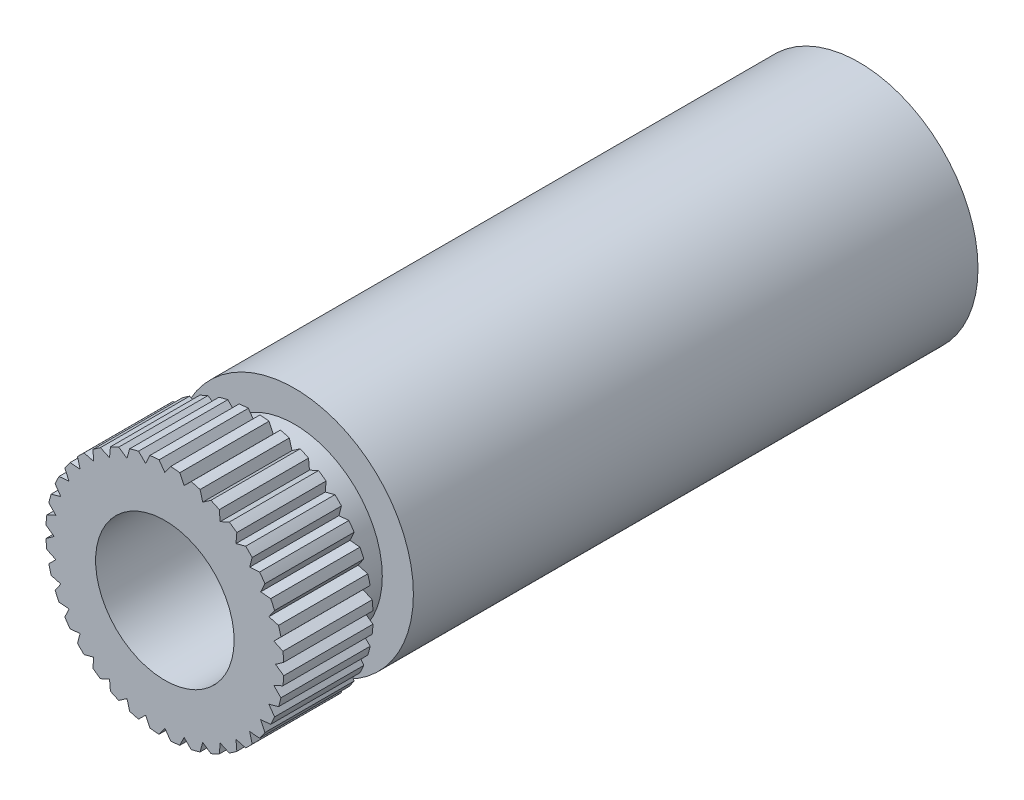
SolidWorks part; units mm, degrees
ref_plane "Front Plane" through (0, 0, 0) normal (0, 0, 1) x (1, 0, 0)
ref_plane "Top Plane" through (0, 0, 0) normal (0, 1, 0) x (1, 0, 0)
ref_plane "Right Plane" through (0, 0, 0) normal (1, 0, 0) x (0, 0, -1)
sketch "Sketch1" plane through (0, 0, 0) normal (0, 0, 1) x (1, 0, 0)
  circle A0 centre (0, 0) radius 6
extrude "Boss-Extrude1" add sketch "Sketch1" against normal blind 35
sketch "Sketch4" plane through (0, 0, 0) normal (0, 0, 1) x (1, 0, 0)
  line L0 (0, 0) -> (5.5808, 0)
  line L1 (6.2992, 0) -> (6.2992, 0.508)
  line L2 (6.2992, 0.508) -> (5.5808, 0)
  line L3 (5.5808, 0) -> (6.2992, -0.508)
  line L4 (6.2992, -0.508) -> (6.2992, 0)
  line L5 (6.2917, -0.5936) -> (5.4961, -0.9691)
  line L6 (5.4961, -0.9691) -> (6.1153, -1.5941)
  line L7 (6.1153, -1.5941) -> (6.2035, -1.0938)
  line L8 (6.2035, -1.0938) -> (6.2917, -0.5936)
  line L9 (6.0931, -1.6771) -> (5.2443, -1.9088)
  line L10 (5.2443, -1.9088) -> (5.7456, -2.6318)
  line L11 (5.7456, -2.6318) -> (5.9193, -2.1545)
  line L12 (5.9193, -2.1545) -> (6.0931, -1.6771)
  line L13 (5.7093, -2.7097) -> (4.8331, -2.7904)
  line L14 (4.8331, -2.7904) -> (5.2013, -3.5895)
  line L15 (5.2013, -3.5895) -> (5.4553, -3.1496)
  line L16 (5.4553, -3.1496) -> (5.7093, -2.7097)
  line L17 (5.152, -3.6599) -> (4.2752, -3.5873)
  line L18 (4.2752, -3.5873) -> (4.4989, -4.4382)
  line L19 (4.4989, -4.4382) -> (4.8255, -4.049)
  line L20 (4.8255, -4.049) -> (5.152, -3.6599)
  line L21 (4.4382, -4.4989) -> (3.5873, -4.2752)
  line L22 (3.5873, -4.2752) -> (3.6599, -5.152)
  line L23 (3.6599, -5.152) -> (4.049, -4.8255)
  line L24 (4.049, -4.8255) -> (4.4382, -4.4989)
  line L25 (3.5895, -5.2013) -> (2.7904, -4.8331)
  line L26 (2.7904, -4.8331) -> (2.7097, -5.7093)
  line L27 (2.7097, -5.7093) -> (3.1496, -5.4553)
  line L28 (3.1496, -5.4553) -> (3.5895, -5.2013)
  line L29 (2.6318, -5.7456) -> (1.9088, -5.2443)
  line L30 (1.9088, -5.2443) -> (1.6771, -6.0931)
  line L31 (1.6771, -6.0931) -> (2.1545, -5.9193)
  line L32 (2.1545, -5.9193) -> (2.6318, -5.7456)
  line L33 (1.5941, -6.1153) -> (0.9691, -5.4961)
  line L34 (0.9691, -5.4961) -> (0.5936, -6.2917)
  line L35 (0.5936, -6.2917) -> (1.0938, -6.2035)
  line L36 (1.0938, -6.2035) -> (1.5941, -6.1153)
  line L37 (0.508, -6.2992) -> (0, -5.5808)
  line L38 (0, -5.5808) -> (-0.508, -6.2992)
  line L39 (-0.508, -6.2992) -> (0, -6.2992)
  line L40 (0, -6.2992) -> (0.508, -6.2992)
  line L41 (-0.5936, -6.2917) -> (-0.9691, -5.4961)
  line L42 (-0.9691, -5.4961) -> (-1.5941, -6.1153)
  line L43 (-1.5941, -6.1153) -> (-1.0938, -6.2035)
  line L44 (-1.0938, -6.2035) -> (-0.5936, -6.2917)
  line L45 (-1.6771, -6.0931) -> (-1.9088, -5.2443)
  line L46 (-1.9088, -5.2443) -> (-2.6318, -5.7456)
  line L47 (-2.6318, -5.7456) -> (-2.1545, -5.9193)
  line L48 (-2.1545, -5.9193) -> (-1.6771, -6.0931)
  line L49 (-2.7097, -5.7093) -> (-2.7904, -4.8331)
  line L50 (-2.7904, -4.8331) -> (-3.5895, -5.2013)
  line L51 (-3.5895, -5.2013) -> (-3.1496, -5.4553)
  line L52 (-3.1496, -5.4553) -> (-2.7097, -5.7093)
  line L53 (-3.6599, -5.152) -> (-3.5873, -4.2752)
  line L54 (-3.5873, -4.2752) -> (-4.4382, -4.4989)
  line L55 (-4.4382, -4.4989) -> (-4.049, -4.8255)
  line L56 (-4.049, -4.8255) -> (-3.6599, -5.152)
  line L57 (-4.4989, -4.4382) -> (-4.2752, -3.5873)
  line L58 (-4.2752, -3.5873) -> (-5.152, -3.6599)
  line L59 (-5.152, -3.6599) -> (-4.8255, -4.049)
  line L60 (-4.8255, -4.049) -> (-4.4989, -4.4382)
  line L61 (-5.2013, -3.5895) -> (-4.8331, -2.7904)
  line L62 (-4.8331, -2.7904) -> (-5.7093, -2.7097)
  line L63 (-5.7093, -2.7097) -> (-5.4553, -3.1496)
  line L64 (-5.4553, -3.1496) -> (-5.2013, -3.5895)
  line L65 (-5.7456, -2.6318) -> (-5.2443, -1.9088)
  line L66 (-5.2443, -1.9088) -> (-6.0931, -1.6771)
  line L67 (-6.0931, -1.6771) -> (-5.9193, -2.1545)
  line L68 (-5.9193, -2.1545) -> (-5.7456, -2.6318)
  line L69 (-6.1153, -1.5941) -> (-5.4961, -0.9691)
  line L70 (-5.4961, -0.9691) -> (-6.2917, -0.5936)
  line L71 (-6.2917, -0.5936) -> (-6.2035, -1.0938)
  line L72 (-6.2035, -1.0938) -> (-6.1153, -1.5941)
  line L73 (-6.2992, -0.508) -> (-5.5808, 0)
  line L74 (-5.5808, 0) -> (-6.2992, 0.508)
  line L75 (-6.2992, 0.508) -> (-6.2992, 0)
  line L76 (-6.2992, 0) -> (-6.2992, -0.508)
  line L77 (-6.2917, 0.5936) -> (-5.4961, 0.9691)
  line L78 (-5.4961, 0.9691) -> (-6.1153, 1.5941)
  line L79 (-6.1153, 1.5941) -> (-6.2035, 1.0938)
  line L80 (-6.2035, 1.0938) -> (-6.2917, 0.5936)
  line L81 (-6.0931, 1.6771) -> (-5.2443, 1.9088)
  line L82 (-5.2443, 1.9088) -> (-5.7456, 2.6318)
  line L83 (-5.7456, 2.6318) -> (-5.9193, 2.1545)
  line L84 (-5.9193, 2.1545) -> (-6.0931, 1.6771)
  line L85 (-5.7093, 2.7097) -> (-4.8331, 2.7904)
  line L86 (-4.8331, 2.7904) -> (-5.2013, 3.5895)
  line L87 (-5.2013, 3.5895) -> (-5.4553, 3.1496)
  line L88 (-5.4553, 3.1496) -> (-5.7093, 2.7097)
  line L89 (-5.152, 3.6599) -> (-4.2752, 3.5873)
  line L90 (-4.2752, 3.5873) -> (-4.4989, 4.4382)
  line L91 (-4.4989, 4.4382) -> (-4.8255, 4.049)
  line L92 (-4.8255, 4.049) -> (-5.152, 3.6599)
  line L93 (-4.4382, 4.4989) -> (-3.5873, 4.2752)
  line L94 (-3.5873, 4.2752) -> (-3.6599, 5.152)
  line L95 (-3.6599, 5.152) -> (-4.049, 4.8255)
  line L96 (-4.049, 4.8255) -> (-4.4382, 4.4989)
  line L97 (-3.5895, 5.2013) -> (-2.7904, 4.8331)
  line L98 (-2.7904, 4.8331) -> (-2.7097, 5.7093)
  line L99 (-2.7097, 5.7093) -> (-3.1496, 5.4553)
  line L100 (-3.1496, 5.4553) -> (-3.5895, 5.2013)
  line L101 (-2.6318, 5.7456) -> (-1.9088, 5.2443)
  line L102 (-1.9088, 5.2443) -> (-1.6771, 6.0931)
  line L103 (-1.6771, 6.0931) -> (-2.1545, 5.9193)
  line L104 (-2.1545, 5.9193) -> (-2.6318, 5.7456)
  line L105 (-1.5941, 6.1153) -> (-0.9691, 5.4961)
  line L106 (-0.9691, 5.4961) -> (-0.5936, 6.2917)
  line L107 (-0.5936, 6.2917) -> (-1.0938, 6.2035)
  line L108 (-1.0938, 6.2035) -> (-1.5941, 6.1153)
  line L109 (-0.508, 6.2992) -> (0, 5.5808)
  line L110 (0, 5.5808) -> (0.508, 6.2992)
  line L111 (0.508, 6.2992) -> (0, 6.2992)
  line L112 (0, 6.2992) -> (-0.508, 6.2992)
  line L113 (0.5936, 6.2917) -> (0.9691, 5.4961)
  line L114 (0.9691, 5.4961) -> (1.5941, 6.1153)
  line L115 (1.5941, 6.1153) -> (1.0938, 6.2035)
  line L116 (1.0938, 6.2035) -> (0.5936, 6.2917)
  line L117 (1.6771, 6.0931) -> (1.9088, 5.2443)
  line L118 (1.9088, 5.2443) -> (2.6318, 5.7456)
  line L119 (2.6318, 5.7456) -> (2.1545, 5.9193)
  line L120 (2.1545, 5.9193) -> (1.6771, 6.0931)
  line L121 (2.7097, 5.7093) -> (2.7904, 4.8331)
  line L122 (2.7904, 4.8331) -> (3.5895, 5.2013)
  line L123 (3.5895, 5.2013) -> (3.1496, 5.4553)
  line L124 (3.1496, 5.4553) -> (2.7097, 5.7093)
  line L125 (3.6599, 5.152) -> (3.5873, 4.2752)
  line L126 (3.5873, 4.2752) -> (4.4382, 4.4989)
  line L127 (4.4382, 4.4989) -> (4.049, 4.8255)
  line L128 (4.049, 4.8255) -> (3.6599, 5.152)
  line L129 (4.4989, 4.4382) -> (4.2752, 3.5873)
  line L130 (4.2752, 3.5873) -> (5.152, 3.6599)
  line L131 (5.152, 3.6599) -> (4.8255, 4.049)
  line L132 (4.8255, 4.049) -> (4.4989, 4.4382)
  line L133 (5.2013, 3.5895) -> (4.8331, 2.7904)
  line L134 (4.8331, 2.7904) -> (5.7093, 2.7097)
  line L135 (5.7093, 2.7097) -> (5.4553, 3.1496)
  line L136 (5.4553, 3.1496) -> (5.2013, 3.5895)
  line L137 (5.7456, 2.6318) -> (5.2443, 1.9088)
  line L138 (5.2443, 1.9088) -> (6.0931, 1.6771)
  line L139 (6.0931, 1.6771) -> (5.9193, 2.1545)
  line L140 (5.9193, 2.1545) -> (5.7456, 2.6318)
  line L141 (6.1153, 1.5941) -> (5.4961, 0.9691)
  line L142 (5.4961, 0.9691) -> (6.2917, 0.5936)
  line L143 (6.2917, 0.5936) -> (6.2035, 1.0938)
  line L144 (6.2035, 1.0938) -> (6.1153, 1.5941)
  point P150 (0, 0)
  circle M146 centre (0, 0) radius 6
  dimension "D1" = 0.508
  dimension "D2" = 0.508
  dimension "D3" = 0.7184
  dimension "D4" = 6.2992
  dimension "D5" = 36
extrude "Cut-Extrude5" cut sketch "Sketch4" against normal blind 4.5 flip side to cut contours L142 L141 L138 L137 L134 L133 L130 L129 L126 L125 L122 L121 L118 L117 L114 L113 L110 L109 L106 L105 L102 L101 L98 L97 L94 L93 L90 L89 L86 L85 L82 L81 L78 L77 M146 region at (5.689, 0.2841, 0)
sketch "Sketch6" plane through (0, 0, -4.5) normal (0, 0, 1) x (1, 0, 0)
  circle A0 centre (0, 0) radius 4.4323
  circle A1 centre (0, 0) radius 6.8805
extrude "Cut-Extrude6" cut sketch "Sketch6" against normal blind 2.032
sketch "Sketch7" plane through (0, 0, 0) normal (0, 0, 1) x (1, 0, 0)
  circle A0 centre (0, 0) radius 3.4925
extrude "Cut-Extrude7" cut sketch "Sketch7" against normal blind 7.112
